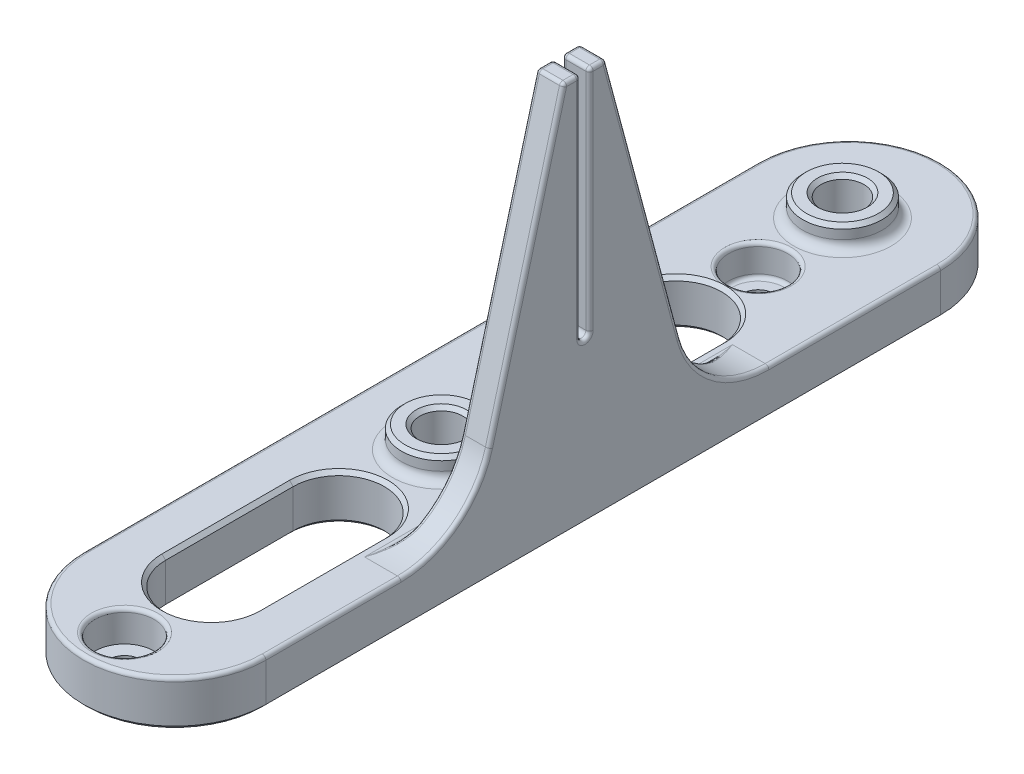
SolidWorks part; units mm, degrees
ref_plane "Front" through (0, 0, 0) normal (0, 0, 1) x (1, 0, 0)
ref_plane "Top" through (0, 0, 0) normal (0, 1, 0) x (1, 0, 0)
ref_plane "Right" through (0, 0, 0) normal (1, 0, 0) x (0, 0, -1)
sketch "Sketch1" plane through (0, 0, 0) normal (0, 1, 0) x (1, 0, 0)
  line L1 (-10, -47) -> (10, -47)
  line L2 (-10, -47) -> (-10, 47)
  line L3 (-10, 47) -> (10, 47)
  line L4 (10, -47) -> (10, 47)
  line L5 (-10, -47) -> (10, 47) construction
  line L6 (-10, 47) -> (10, -47) construction
  point P0 (0, 0)
  dimension "D1" = 94
  dimension "D2" = 20
extrude "Boss-Extrude1" add sketch "Sketch1" along normal blind 20
sketch "Sketch2" plane through (0, 0, 0) normal (1, 0, 0) x (0, 0, -1)
  line L0 (-47, 20) -> (-47, 5)
  line L1 (-47, 20) -> (47, 20) construction
  line L2 (-47, 5) -> (47, 5)
  line L3 (47, 5) -> (47, 20)
  line L5 (-47, 20) -> (-47, 0) construction
  line L6 (-47, 0) -> (47, 0) construction
  line L7 (-47, 20) -> (47, 20)
  line L8 (47, 20) -> (47, 0) construction
  dimension "D4" = 5
extrude "Cut-Extrude1" cut sketch "Sketch2" against normal mid plane 20
sketch "Sketch4" plane through (0, 5, 0) normal (0, 1, 0) x (1, 0, 0)
  line L0 (0, 3.5) -> (0, 18) construction
  line L1 (-5, 3.5) -> (-5, 18)
  line L2 (5, 3.5) -> (5, 18)
  line L3 (0, -33) -> (0, -19) construction
  line L4 (-5, -33) -> (-5, -19)
  line L5 (5, -33) -> (5, -19)
  line L6 (-10, -47) -> (10, -47) construction
  line L7 (-10, 47) -> (10, 47) construction
  arc A0 (-5, 3.5) -> (5, 3.5) centre (0, 3.5) ccw
  arc A1 (5, 18) -> (-5, 18) centre (0, 18) ccw
  arc A2 (-5, -33) -> (5, -33) centre (0, -33) ccw
  arc A3 (5, -19) -> (-5, -19) centre (0, -19) ccw
  point P3 (0, 10.75)
  point P10 (0, -26)
  dimension "D1" = 10
  dimension "D2" = 14.5
  dimension "D3" = 14
  dimension "D4" = 29
  dimension "D5" = 14
extrude "Cut-Extrude2" cut sketch "Sketch4" against normal through all
sketch "Sketch11" plane through (0, 5, 0) normal (0, 1, 0) x (1, 0, 0)
  line L0 (-10, 47) -> (10, 47)
  line L1 (10, 47) -> (10, 37)
  line L2 (10, 47) -> (10, -47) construction
  line L3 (-10, -47) -> (-10, 47) construction
  line L4 (-10, 37) -> (-10, 47)
  line L5 (-10, -47) -> (-10, 47) construction
  line L6 (10, 47) -> (10, -47) construction
  line L7 (-10, -47) -> (10, -47) construction
  line L8 (-10, -37) -> (-10, -47)
  line L9 (-10, -47) -> (10, -47)
  line L10 (10, -47) -> (10, -37)
  arc A0 (10, 37) -> (-10, 37) centre (0, 37) ccw
  arc A1 (-10, -37) -> (10, -37) centre (0, -37) ccw
  line M6 (10, 47) -> (-10, 47)
  line M7 (-10, 47) -> (-10, -47)
  line M9 (10, -47) -> (10, 47)
  line M15 (-10, -47) -> (10, -47)
extrude "Cut-Extrude4" cut sketch "Sketch11" against normal through all contours A0 L0 M7 | A0 M9 M6 | A1 L9 M9 | A1 M7 M15 region at (-7.7663, 5, -44.7663) region at (7.7663, 5, -44.7663) region at (-7.7663, 5, 44.7663) region at (7.7663, 5, 44.7663)
chamfer "Chamfer2" distance 0.4 angle 45 12 edges at (-10, 0, 0) (10, 0, 0) (-5, 0, -10.75) (0, 0, -23) (5, 0, -10.75) (0, 0, 1.5) (0, 0, -47) (0, 0, 47) (-5, 0, 26) (0, 0, 14) (5, 0, 26) (0, 0, 38)
chamfer "Chamfer3" distance 0.4 angle 45 8 edges at (5, 5, -10.75) (0, 5, -23) (0, 5, 1.5) (-5, 5, -10.75) (5, 5, 26) (0, 5, 14) (0, 5, 38) (-5, 5, 26)
sketch "Sketch12" plane through (0, 5, 0) normal (0, 1, 0) x (1, 0, 0)
  circle A0 centre (0, 36.25) radius 4.35
  circle A2 centre (0, -7.75) radius 4.35
  arc A3 (10, 37) -> (-10, 37) centre (0, 37) ccw construction
  point P8 (0, 47)
  dimension "D1" = 8.7
  dimension "D2" = 44
  dimension "D3" = 10.75
extrude "Boss-Extrude4" add sketch "Sketch12" along normal blind 2.4
fillet "Fillet7" radius 1 2 edges at (0, 5, -40.6) (0, 5, 3.4)
sketch "Sketch13" plane through (0, 7.4, 0) normal (0, 1, 0) x (1, 0, 0)
  circle A0 centre (0, 36.25) radius 2.35
  circle A1 centre (0, -7.75) radius 2.35
  dimension "D1" = 4.7
extrude "Cut-Extrude5" cut sketch "Sketch13" against normal through all
chamfer "Chamfer8" distance 0.4 angle 45 6 edges at (0, 7.4, -33.9) (0, 7.4, -31.9) (0, 0, -33.9) (0, 0, 10.1) (0, 7.4, 10.1) (0, 7.4, 12.1)
hole_wizard "CBORE for M3 Hex Socket Head Cap Screw1" positions "Sketch14" profile "Sketch15" counterbore size "M3" standard "ISO"
sketch "Sketch14" plane through (0, 5, 0) normal (0, 1, 0) x (1, 0, 0)
  line L0 (0, -50) -> (0, 50) construction
  point P0 (0, 27)
  point P2 (0, -42.5)
  dimension "D1" = 42.5
  dimension "D2" = 27
sketch "Sketch15" plane through (0, 5, -27) normal (1, 0, 0) x (0, 0, 1)
  line L0 (0, 0) -> (0, 15.0215)
  line L1 (0, 15.0215) -> (1.7, 14)
  line L2 (1.7, 14) -> (1.7, 3.4)
  line L3 (1.7, 3.4) -> (3.25, 3.4)
  line L4 (3.25, 3.4) -> (3.25, 0)
  line L5 (3.25, 0) -> (0, 0)
  line L10 (0, 15.0215) -> (-1.7, 14) construction
  line L11 (0, -6.35) -> (0, 107.95) construction
  dimension "Hole Dia." = 3.4
  dimension "Hole Depth" = 14
  dimension "C'Bore Dia." = 6.5
  dimension "C'Bore Depth" = 3.4
  dimension "Drill Angle" = 118
sketch "Sketch16" plane through (10, 0, 0) normal (1, 0, 0) x (0, 0, -1)
  line L0 (-14.5, 5) -> (-4.3179, 43)
  line L1 (-37, 5) -> (37, 5) construction
  line L2 (-4.3179, 43) -> (-2.5, 43)
  line L3 (-2.5, 43) -> (-2.5, 18)
  line L4 (-1.5, 18) -> (-1.5, 43)
  line L5 (-1.5, 43) -> (0.3179, 43)
  line L6 (0.3179, 43) -> (10.5, 5)
  line L7 (10.5, 5) -> (-14.5, 5)
  line L8 (-37, 0.4) -> (-37, 5) construction
  arc A0 (-2.5, 18) -> (-1.5, 18) centre (-2, 18) ccw
  point P13 (-2, 5)
  dimension "D1" = 25
  dimension "D2" = 38
  dimension "D3" = 1
  dimension "D4" = 30
  dimension "D5" = 25
  dimension "D6" = 35
extrude "Boss-Extrude5" add sketch "Sketch16" against normal blind 3
fillet "Fillet8" radius 10 2 edges at (8.5, 5, 14.5) (8.5, 5, -10.5)
fillet "Fillet9" radius 1 1 edges at (7, 5, 2)
sketch "Sketch17" plane through (0, 0, 0) normal (0, -1, 0) x (1, 0, 0)
  line L0 (10, 40.18) -> (10, 37)
  line L1 (10, 40.18) -> (9.4809, 40.18)
  arc A0 (10, 37) -> (9.4809, 40.18) centre (0, 37) ccw
fillet "Fillet10" radius 0.4 32 edges at (10, 30.5, 2.5) (10, 17.5, 2) (7, 30.5, 1.5) (7, 17.5, 2) (6.75, 5.3385, 19.5934) (7, 8.6286, 14.4658) (6.75, 5.3385, -15.5934) (7, 8.6286, -10.4658) (10, 27.7059, -4.416) (10, 7.0665, -12.0857) (0, 5, 47) (-10, 5, 0) (0, 5, -47) (8.5, 43, 4.3179) (7, 43, 3.409) (8.5, 43, 2.5) (10, 43, 3.409) (8.5, 43, 1.5) (7, 43, 0.591) (8.5, 43, -0.3179) (10, 43, 0.591) (10, 27.7059, 8.416) (10, 30.5, 1.5) (7, 30.5, 2.5) (7, 27.7059, 8.416) (7, 27.7059, -4.416) (10, 5, -27.5866) (0, 5, -23.75) (0, 1.6, -23.75) (0, 5, 45.75) (10, 7.0665, 16.0857) (10, 5, 29.5866)
